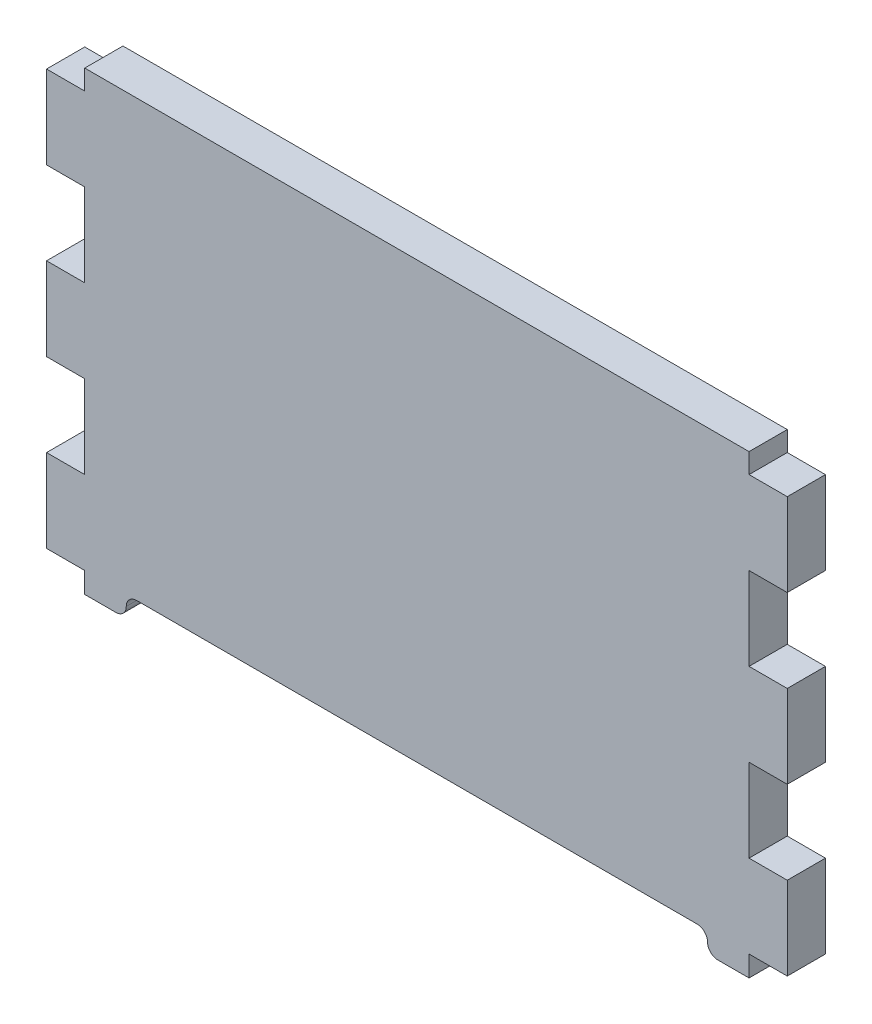
SolidWorks part; units mm, degrees
ref_plane "Front Plane" through (0, 0, 0) normal (0, 0, 1) x (1, 0, 0)
ref_plane "Top Plane" through (0, 0, 0) normal (0, 1, 0) x (1, 0, 0)
ref_plane "Right Plane" through (0, 0, 0) normal (1, 0, 0) x (0, 0, -1)
sketch "Sketch1" plane through (0, 0, 0) normal (0, 0, 1) x (1, 0, 0)
  line L0 (-56.642, -12.7) -> (-50.8, -12.7) construction
  line L1 (50.8, -22.225) -> (44.45, -22.225)
  line L2 (50.8, -22.225) -> (50.8, -19.05)
  line L3 (-50.8, 44.45) -> (-50.8, 47.498)
  line L4 (-50.8, -22.225) -> (-50.8, -19.05)
  line L5 (0, 22.225) -> (0, -22.225) construction
  line L6 (50.8, 0) -> (-50.8, 0) construction
  line L7 (-56.642, 6.35) -> (-50.8, 6.35)
  line L8 (-56.642, 6.35) -> (-56.642, 19.05)
  line L9 (-56.642, 19.05) -> (-50.8, 19.05)
  line L10 (-50.8, -6.35) -> (-50.8, 6.35)
  line L11 (-53.721, 19.05) -> (-53.721, 6.35) construction
  line L12 (-56.642, 12.7) -> (-50.8, 12.7) construction
  line L13 (-53.721, -19.05) -> (-53.721, -6.35) construction
  line L14 (50.8, -6.35) -> (50.8, 6.35)
  line L15 (-56.642, -19.05) -> (-50.8, -19.05)
  line L16 (-56.642, -6.35) -> (-56.642, -19.05)
  line L17 (-56.642, -6.35) -> (-50.8, -6.35)
  line L18 (53.721, -19.05) -> (53.721, -6.35) construction
  line L19 (56.642, 12.7) -> (50.8, 12.7) construction
  line L20 (53.721, 19.05) -> (53.721, 6.35) construction
  line L21 (56.642, -12.7) -> (50.8, -12.7) construction
  line L22 (56.642, -6.35) -> (50.8, -6.35)
  line L23 (56.642, -6.35) -> (56.642, -19.05)
  line L24 (56.642, -19.05) -> (50.8, -19.05)
  line L25 (50.8, 19.05) -> (50.8, 31.75)
  line L26 (-50.8, 19.05) -> (-50.8, 31.75)
  line L27 (56.642, 19.05) -> (50.8, 19.05)
  line L28 (56.642, 6.35) -> (56.642, 19.05)
  line L29 (56.642, 6.35) -> (50.8, 6.35)
  line L30 (50.8, -22.225) -> (50.8, -19.05)
  line L32 (-44.45, -19.05) -> (44.45, -19.05)
  line L33 (50.8, 25.4) -> (-50.8, 25.4) construction
  line L34 (-44.45, -19.05) -> (-44.45, -22.225)
  line L38 (-44.45, -22.225) -> (-50.8, -22.225)
  line L39 (44.45, -19.05) -> (44.45, -22.225)
  line L40 (50.8, -6.35) -> (50.8, 6.35)
  line L41 (53.721, 31.75) -> (53.721, 44.45) construction
  line L42 (56.642, 38.1) -> (50.8, 38.1) construction
  line L43 (-56.642, 38.1) -> (-50.8, 38.1) construction
  line L44 (-53.721, 31.75) -> (-53.721, 44.45) construction
  line L45 (56.642, 44.45) -> (50.8, 44.45)
  line L46 (56.642, 44.45) -> (56.642, 31.75)
  line L47 (56.642, 31.75) -> (50.8, 31.75)
  line L48 (-56.642, 31.75) -> (-50.8, 31.75)
  line L49 (-56.642, 44.45) -> (-56.642, 31.75)
  line L50 (-56.642, 44.45) -> (-50.8, 44.45)
  line L52 (-50.8, 47.498) -> (50.8, 47.498)
  line L53 (50.8, 44.45) -> (50.8, 47.498)
  point P0 (0, 0)
  point P4 (-53.721, 12.7)
  point P22 (-53.721, -12.7)
  point P39 (53.721, -12.7)
  point P40 (53.721, 12.7)
  point P72 (53.721, 38.1)
  point P73 (-53.721, 38.1)
  dimension "D3" = 12.7
  dimension "D4" = 5.842
  dimension "D5" = 3.048
  dimension "D6" = 101.6
extrude "Boss-Extrude1" add sketch "Sketch1" along normal blind 5.842 contours L39 L1 L2 L30 L14 L29 L28 L27 L9 L8 L7 L10 L17 L16 L15 L4 L38 L34 region at (0, 13.9364, 0)
fillet "Fillet1" radius 1.5875 4 edges at (-44.45, -19.05, 2.921) (44.45, -19.05, 2.921) (44.45, -22.225, 2.921) (-44.45, -22.225, 2.921)
